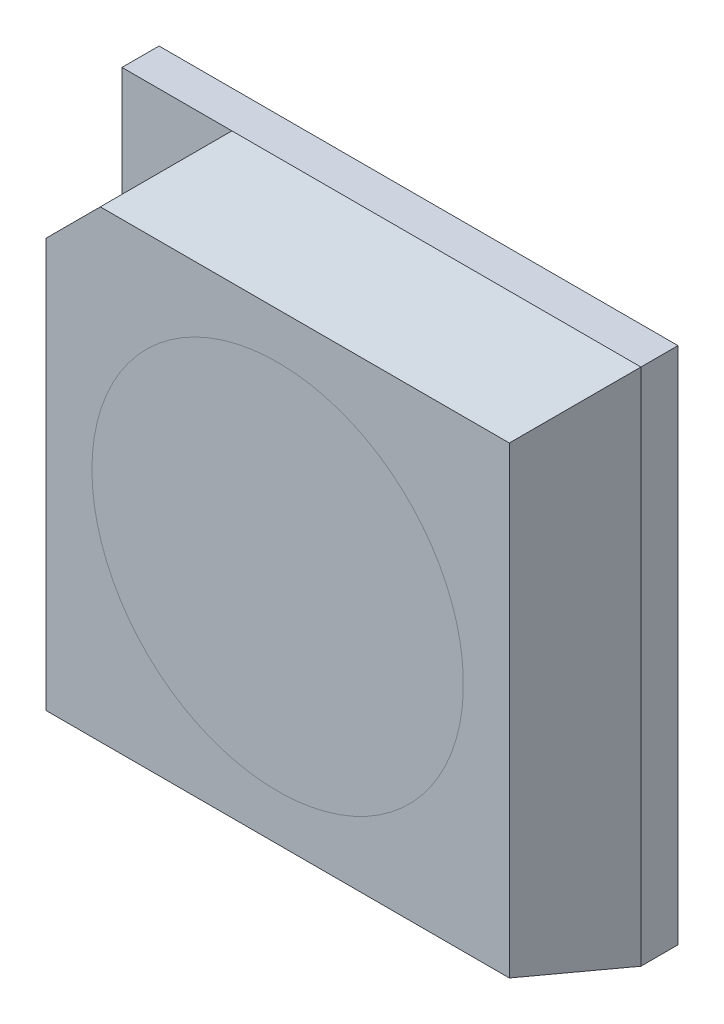
SolidWorks part; units mm, degrees
ref_plane "Front" through (0, 0, 0) normal (0, 0, 1) x (1, 0, 0)
ref_plane "Top" through (0, 0, 0) normal (0, 1, 0) x (1, 0, 0)
ref_plane "Right" through (0, 0, 0) normal (1, 0, 0) x (0, 0, -1)
sketch "Sketch1" plane through (0, 0, 0) normal (0, 0, 1) x (1, 0, 0)
  line L1 (-1.75, -1.75) -> (1.75, -1.75)
  line L2 (-1.75, -1.75) -> (-1.75, 1.75)
  line L3 (-1.75, 1.75) -> (1.75, 1.75)
  line L4 (1.75, -1.75) -> (1.75, 1.75)
  line L5 (-1.75, -1.75) -> (1.75, 1.75) construction
  line L6 (-1.75, 1.75) -> (1.75, -1.75) construction
  point P0 (0, 0)
  dimension "D1" = 3.5
extrude "Boss-Extrude1" add sketch "Sketch1" against normal blind 0.25
extrude "Boss-Extrude2" add sketch "Sketch1<2>" along normal blind 0.7 draft 15 separate body
sketch "Sketch1<2>" plane through (0, 0, 0) normal (0, 0, 1) x (1, 0, 0) same geometry as "Sketch1"
sketch "Sketch2" plane through (0, 0, 0) normal (0, 0, 1) x (1, 0, 0)
  line L0 (1.75, 1.75) -> (-1.75, 1.75) construction
  line L1 (0.5665, 1.3677) -> (-0.5665, 1.3677)
  line L2 (-0.5665, 1.3677) -> (-1.3677, 0.5665)
  line L3 (-1.3677, 0.5665) -> (-1.3677, -0.5665)
  line L4 (-1.3677, -0.5665) -> (-0.5665, -1.3677)
  line L5 (-0.5665, -1.3677) -> (0.5665, -1.3677)
  line L6 (0.5665, -1.3677) -> (1.3677, -0.5665)
  line L7 (1.3677, -0.5665) -> (1.3677, 0.5665)
  line L8 (1.3677, 0.5665) -> (0.5665, 1.3677)
  line L9 (0.4837, 1.1677) -> (-0.4837, 1.1677)
  line L10 (-0.4837, 1.1677) -> (-1.1677, 0.4837)
  line L11 (-1.1677, 0.4837) -> (-1.1677, -0.4837)
  line L12 (-1.1677, -0.4837) -> (-0.4837, -1.1677)
  line L13 (-0.4837, -1.1677) -> (0.4837, -1.1677)
  line L14 (0.4837, -1.1677) -> (1.1677, -0.4837)
  line L15 (1.1677, -0.4837) -> (1.1677, 0.4837)
  line L16 (1.1677, 0.4837) -> (0.4837, 1.1677)
  circle A0 centre (0, 0) radius 1.3677 construction
  circle A1 centre (0, 0) radius 1.1677 construction
  circle A2 centre (-0.4837, 0.6007) radius 0.2403
  circle A3 centre (0.5665, 0.1662) radius 0.2953
  circle A4 centre (-0.4281, -0.428) radius 0.3388
  dimension "D1" = 0.2
extrude "Boss-Extrude4" add sketch "Sketch2" along normal blind 0.25 separate body contours L7 L8 L1 L2 L3 L4 L5 L6 L16 L15 L14 L13 L12 L11 L10 L9 | A2 | A4 | A3 region at (0.9398, 0.9398, 0) region at (-0.4837, 0.6007, 0) region at (0.5665, 0.1662, 0) region at (-0.4281, -0.428, 0)
sketch "Sketch3" plane through (0, 0, 0) normal (0, 0, 1) x (1, 0, 0)
  line L0 (-1.75, 1.0086) -> (-1.0086, 1.75)
  line L1 (-1.75, 1.75) -> (-1.75, -1.75) construction
  line L2 (1.75, 1.75) -> (-1.75, 1.75) construction
  line L3 (-1.0086, 1.75) -> (-1.75, 1.75)
  line L4 (-1.75, 1.75) -> (-1.75, -1.75) construction
  line L5 (-1.75, 1.75) -> (-1.75, 1.0086)
  dimension "D1" = 45
extrude "Cut-Extrude1" cut sketch "Sketch3" along normal through all
chamfer "Chamfer1" [suppressed] distance 0.4 angle 45
sketch "Sketch4" plane through (0, 0, 0.7) normal (0, 0, 1) x (1, 0, 0)
  circle A0 centre (0, 0) radius 1.2526
wrap "Wrap1" sketch "Sketch4" wrap type scribe source sketch "Sketch4" face at (-0.2392, 0.2392, 0.7)
